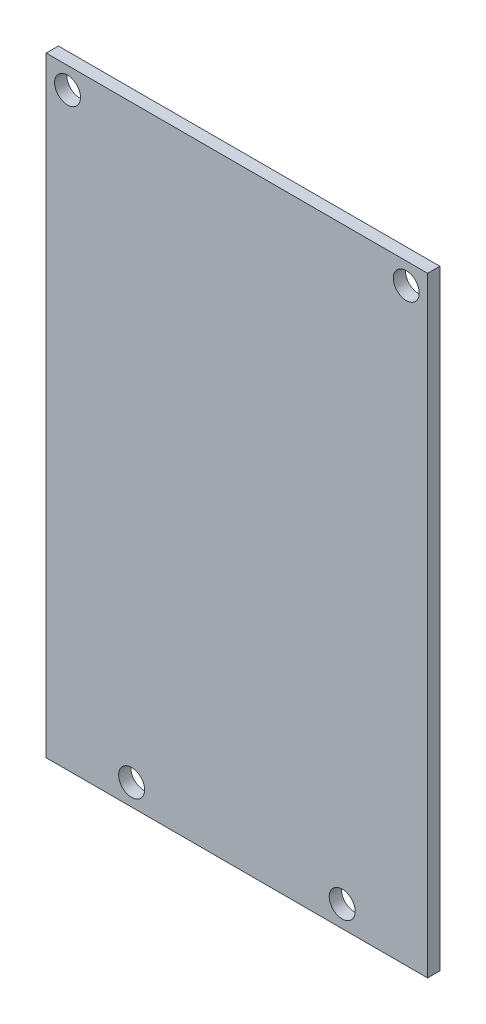
SolidWorks part; units mm, degrees
ref_plane "Plan de face" through (0, 0, 0) normal (0, 0, 1) x (1, 0, 0)
ref_plane "Plan de dessus" through (0, 0, 0) normal (0, 1, 0) x (1, 0, 0)
ref_plane "Plan de droite" through (0, 0, 0) normal (1, 0, 0) x (0, 0, -1)
sketch "Esquisse1" plane through (0, 0, 0) normal (0, 0, 1) x (1, 0, 0)
  line L1 (-25, 40) -> (25, 40)
  line L2 (-25, 40) -> (-25, -40)
  line L3 (-25, -40) -> (25, -40)
  line L4 (25, 40) -> (25, -40)
  line L5 (-25, 40) -> (25, -40) construction
  line L6 (-25, -40) -> (25, 40) construction
  point P0 (0, 0)
  dimension "D1" = 50
  dimension "D2" = 80
extrude "Boss.-Extru.1" add sketch "Esquisse1" along normal blind 1.6 contours L2 L3 L4 L1
hole_wizard "Dégagement M31" positions "Esquisse2" profile "Esquisse4" hole size "M3" standard "Ansi Metric" end condition through all
sketch "Esquisse2" plane through (0, 0, 1.6) normal (0, 0, 1) x (1, 0, 0)
  line L0 (-22.2, 37.2) -> (22.2, 37.2) construction
  line L2 (-25, 40) -> (25, 40) construction
  line L3 (22.2, 37.2) -> (25, 37.2) construction
  line L4 (25, 40) -> (25, -40) construction
  line L6 (22.2, 37.2) -> (22.2, 40) construction
  line L8 (-13.8, -37.2) -> (13.8, -37.2) construction
  line L10 (-25, -40) -> (25, -40) construction
  line L11 (-5.8338, -37.2) -> (-5.8338, -40) construction
  point P0 (-22.2, 37.2)
  point P2 (22.2, 37.2)
  point P4 (13.8, -37.2)
  point P6 (-13.8, -37.2)
  point P15 (0, 40)
  point P16 (0, 37.2)
  point P32 (0, -40)
  point P33 (0, -37.2)
  dimension "D1" = 44.4
  dimension "D2" = 27.6
  dimension "D3" = 2.8
sketch "Esquisse4" plane through (-22.2, 37.2, 1.6) normal (1, 0, 0) x (0, -1, 0)
  line L0 (0, 0) -> (0, 1.6)
  line L1 (0, 1.6) -> (1.7, 1.6)
  line L2 (1.7, 1.6) -> (1.7, 0)
  line L5 (1.7, 0) -> (0, 0)
  line L11 (0, -6.35) -> (0, 107.95) construction
  dimension "Diamètre du perçage jusqu'au prochain" = 3.4
  dimension "Profondeur du perçage jusqu'au prochain" = 1.6
